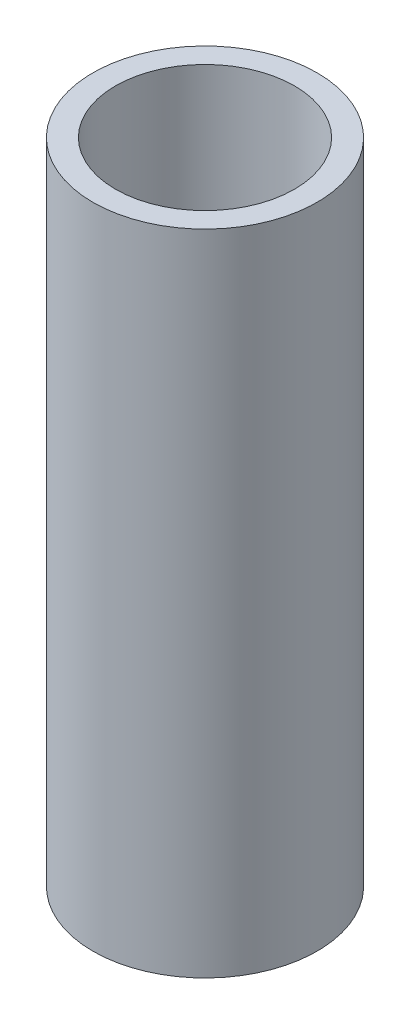
SolidWorks part; units mm, degrees
ref_plane "Front Plane" through (0, 0, 0) normal (0, 0, 1) x (1, 0, 0)
ref_plane "Top Plane" through (0, 0, 0) normal (0, 1, 0) x (1, 0, 0)
ref_plane "Right Plane" through (0, 0, 0) normal (1, 0, 0) x (0, 0, -1)
sketch "Sketch1" plane through (0, 0, 0) normal (0, 1, 0) x (1, 0, 0)
  circle A0 centre (0, 0) radius 37.5
  dimension "SLEEVE_OD" = 75
extrude "Boss-Extrude1" add sketch "Sketch1" along normal blind 216.8707
sketch "Sketch2" plane through (0, 0, 0) normal (0, 1, 0) x (1, 0, 0)
  circle A0 centre (0, 0) radius 29.938
  dimension "BORE_D" = 59.876
extrude "Cut-Extrude1" cut sketch "Sketch2" along normal through all
chamfer "Chamfer1" distance 3.9435 angle 57.878 rebuild error yes
